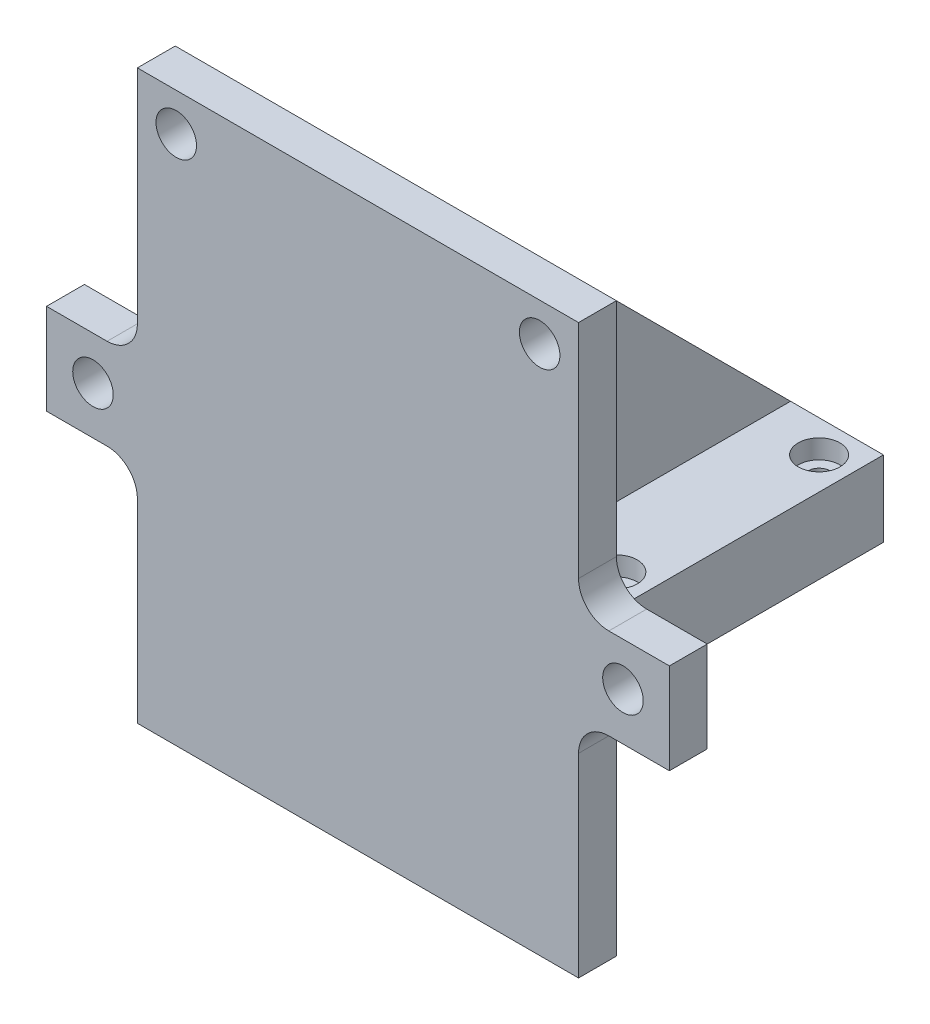
SolidWorks part; units mm, degrees
ref_plane "Front Plane" through (0, 0, 0) normal (0, 0, 1) x (1, 0, 0)
ref_plane "Top Plane" through (0, 0, 0) normal (0, 1, 0) x (1, 0, 0)
ref_plane "Right Plane" through (0, 0, 0) normal (1, 0, 0) x (0, 0, -1)
sketch "Sketch1" plane through (0, 0, 0) normal (0, 1, 0) x (1, 0, 0)
  line L0 (5.5, 2.45) -> (5.5, 0) construction
  line L1 (0, 0) -> (37, 0)
  line L2 (0, 0) -> (0, 22.4)
  line L3 (0, 22.4) -> (37, 22.4)
  line L4 (37, 0) -> (37, 22.4)
  line L5 (5.5, 19.95) -> (5.5, 22.4) construction
  line L6 (34.3, 19.7) -> (34.3, 22.4) construction
  line L7 (34.3, 2.7) -> (34.3, 0) construction
  point P5 (5.5, 19.95)
  point P6 (5.5, 2.45)
  point P7 (34.3, 19.7)
  point P8 (34.3, 2.7)
  dimension "D1" = 37
  dimension "D2" = 22.4
  dimension "D3" = 17.5
  dimension "D4" = 5.5
  dimension "D5" = 2.7
  dimension "D6" = 2.7
extrude "Boss-Extrude1" add sketch "Sketch1" along normal blind 6.35
sketch "Sketch7" plane through (37, 0, 0) normal (1, 0, 0) x (0, 0, -1)
  line L0 (0, -18.86) -> (0, 28.75)
  line L1 (0, 28.75) -> (-3.175, 28.75)
  line L2 (-3.175, 28.75) -> (-3.175, -18.86)
  line L3 (-3.175, -18.86) -> (0, -18.86)
  line L4 (0, 0) -> (22.4, 0) construction
  dimension "D1" = 3.175
  dimension "D2" = 18.86
  dimension "D3" = 22.4
extrude "Boss-Extrude2" add sketch "Sketch7" against normal up to surface (37 mm away) up to face at (0, 3.175, -11.2)
ref_plane "CBORE PLANE" through (0, 13.97, 0) normal (0, 1, 0) x (1, 0, 0)
hole_wizard "CBORE for M3 SHCS3" positions "Sketch12" profile "Sketch13" counterbore size "M3" standard "ANSI Metric" end condition through all
sketch "Sketch12" plane through (0, 13.97, 0) normal (0, 1, 0) x (1, 0, 0)
  point P0 (5.5, 2.45)
  point P3 (5.5, 19.95)
sketch "Sketch13" plane through (5.5, 13.97, -2.45) normal (1, 0, 0) x (0, 0, 1)
  line L0 (0, 0) -> (0, 32.83)
  line L1 (0, 32.83) -> (1.7, 32.83)
  line L3 (1.7, 32.83) -> (1.7, 10.62)
  line L4 (1.7, 10.62) -> (3.25, 10.62)
  line L5 (3.25, 10.62) -> (3.25, 0)
  line L7 (3.25, 0) -> (0, 0)
  line L11 (0, -6.35) -> (0, 107.95) construction
  dimension "Thru Hole Dia." = 3.4
  dimension "Thru Hole Depth" = 32.83
  dimension "C'Bore Dia." = 6.5
  dimension "C'Bore Depth" = 10.62
hole_wizard "CBORE for M1.6 SHCS1" positions "Sketch14" profile "Sketch15" counterbore size "M1.6" standard "ANSI Metric" end condition through all
sketch "Sketch14" plane through (0, 6.35, 0) normal (0, 1, 0) x (1, 0, 0)
  point P0 (34.3, 19.7)
  point P3 (34.3, 2.7)
sketch "Sketch15" plane through (34.3, 6.35, -19.7) normal (1, 0, 0) x (0, 0, 1)
  line L0 (0, 0) -> (0, 25.21)
  line L1 (0, 25.21) -> (0.9, 25.21)
  line L3 (0.9, 25.21) -> (0.9, 1.6)
  line L4 (0.9, 1.6) -> (1.75, 1.6)
  line L5 (1.75, 1.6) -> (1.75, 0)
  line L7 (1.75, 0) -> (0, 0)
  line L11 (0, -6.35) -> (0, 107.95) construction
  dimension "Thru Hole Dia." = 1.8
  dimension "Thru Hole Depth" = 25.21
  dimension "C'Bore Dia." = 3.5
  dimension "C'Bore Depth" = 1.6
sketch "Sketch16" plane through (0, 0, 0) normal (-1, 0, 0) x (0, 0, 1)
  line L0 (-22.4, 6.35) -> (0, 6.35)
  line L1 (0, 6.35) -> (0, 28.75)
  line L2 (0, 28.75) -> (-22.4, 6.35)
extrude "Boss-Extrude3" add sketch "Sketch16" against normal blind 3.175 from offset 10.16 offset against normal yes
extrude "Boss-Extrude4" add sketch "Sketch16<2>" along normal blind 3.175 from offset 29.21 offset against normal yes
sketch "Sketch16<2>" plane through (0, 0, 0) normal (-1, 0, 0) x (0, 0, 1) same geometry as "Sketch16"
sketch "Sketch18" plane through (0, 0, 0) normal (0, 0, 1) x (1, 0, 0)
  line L9 (37, 0) -> (44.62, 0)
  line L10 (37, 0) -> (37, 7.62)
  line L11 (37, 7.62) -> (44.62, 7.62)
  line L12 (44.62, 0) -> (44.62, 7.62)
  line L13 (0, 0) -> (-7.62, 0)
  line L14 (0, 0) -> (0, 7.62)
  line L15 (0, 7.62) -> (-7.62, 7.62)
  line L16 (-7.62, 0) -> (-7.62, 7.62)
  dimension "D1" = 7.62
  dimension "D2" = 7.62
extrude "Boss-Extrude5" add sketch "Sketch18" along normal through all
sketch "Mounting Hole Locations" plane through (0, 0, 0) normal (0, 0, -1) x (-1, 0, 0)
  line L0 (-18.5, -18.86) -> (-18.5, 28.75) construction
  line L1 (0, -18.86) -> (-37, -18.86) construction
  line L2 (-13.335, 28.75) -> (-26.035, 28.75) construction
  line L3 (-29.21, 28.75) -> (-37, 28.75) construction
  point P2 (-33.74, 25.575)
  point P5 (0, 0)
  point P13 (-40.725, 3.985)
  point P16 (-3.26, 25.575)
  point P17 (3.725, 3.985)
  dimension "D1" = 21.59
  dimension "D2" = 15.24
  dimension "D3" = 3.175
  dimension "D4" = 22.225
hole_wizard "M3 Clearance Hole1" positions "Sketch19" profile "Sketch20" hole size "M3" standard "ANSI Metric" end condition through all
sketch "Sketch19" plane through (0, 0, 0) normal (0, 0, -1) x (-1, 0, 0)
  point P0 (-40.725, 3.985)
  point P3 (-33.74, 25.575)
  point P6 (-3.26, 25.575)
  point P9 (3.725, 3.985)
sketch "Sketch20" plane through (40.725, 3.985, 0) normal (1, 0, 0) x (0, 1, 0)
  line L0 (0, 0) -> (0, 3.175)
  line L1 (0, 3.175) -> (1.7, 3.175)
  line L2 (1.7, 3.175) -> (1.7, 0)
  line L5 (1.7, 0) -> (0, 0)
  line L11 (0, -6.35) -> (0, 107.95) construction
  dimension "Thru Hole Dia." = 3.4
  dimension "Thru Hole Depth" = 3.175
fillet "Fillet1" radius 2.54 9 edges at (13.335, 6.35, -11.2) (13.335, 17.55, 0) (26.035, 6.35, -11.2) (26.035, 17.55, 0) (19.685, 6.35, 0) (0, 7.62, 1.5875) (0, 0, 1.5875) (37, 0, 1.5875) (37, 7.62, 1.5875)
fillet "Fillet2" radius 1.27 2 edges at (3.3646, 4.85, -22.4) (7.6354, 4.85, -22.4)
